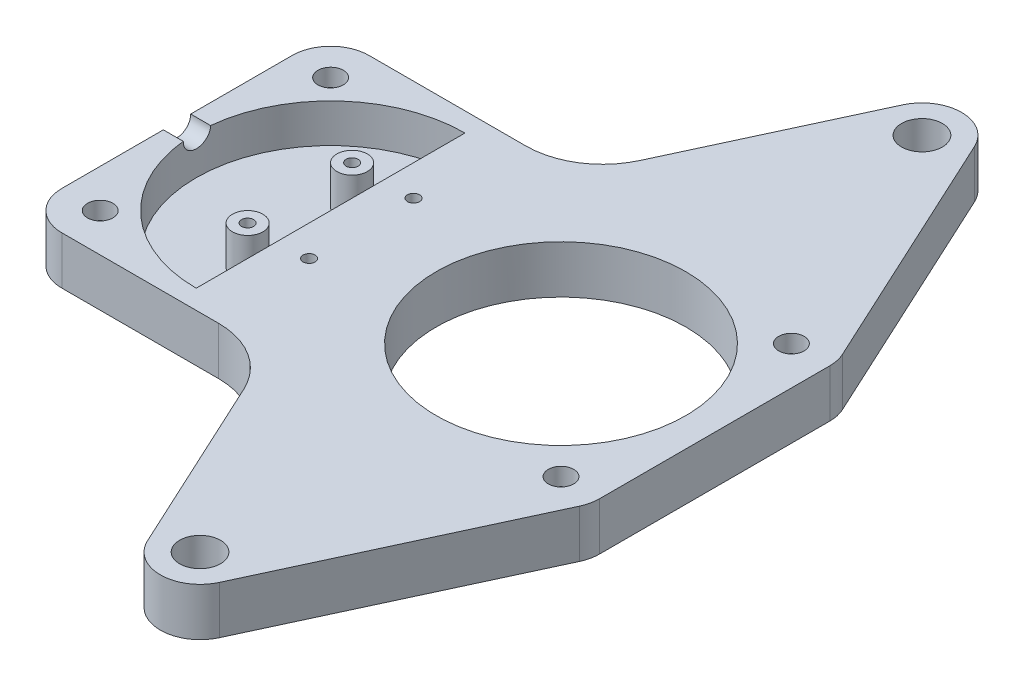
SolidWorks part; units mm, degrees
ref_plane "Front Plane" through (0, 0, 0) normal (0, 0, 1) x (1, 0, 0)
ref_plane "Top Plane" through (0, 0, 0) normal (0, 1, 0) x (1, 0, 0)
ref_plane "Right Plane" through (0, 0, 0) normal (1, 0, 0) x (0, 0, -1)
sketch "Sketch1" plane through (0, 0, 0) normal (0, 1, 0) x (1, 0, 0)
  line L0 (38.1, 19.05) -> (38.1, 25.4) construction
  line L1 (-19.05, -25.4) -> (57.15, -25.4)
  line L2 (-25.4, -19.05) -> (-25.4, 19.05)
  line L3 (-19.05, 25.4) -> (57.15, 25.4)
  line L4 (63.5, -19.05) -> (63.5, 19.05)
  line L5 (-25.4, -25.4) -> (63.5, 25.4) construction
  line L6 (-25.4, 25.4) -> (63.5, -25.4) construction
  line L7 (57.15, 0) -> (63.5, 0) construction
  line L9 (-7.62, -11.176) -> (7.62, -11.176) construction
  line L10 (-7.62, -11.176) -> (-7.62, 11.176) construction
  line L11 (-7.62, 11.176) -> (7.62, 11.176) construction
  line L12 (7.62, -11.176) -> (7.62, 11.176) construction
  line L13 (-7.62, -11.176) -> (7.62, 11.176) construction
  line L14 (-7.62, 11.176) -> (7.62, -11.176) construction
  circle A0 centre (0, 0) radius 19.05 construction
  circle A1 centre (38.1, 0) radius 19.05 construction
  circle A2 centre (38.1, 0) radius 12.7 construction
  circle A3 centre (38.1, 0) radius 20.6375
  arc A4 (-25.4, 19.05) -> (-19.05, 25.4) centre (-19.05, 19.05) cw
  arc A5 (-19.05, -25.4) -> (-25.4, -19.05) centre (-19.05, -19.05) cw
  arc A6 (57.15, -25.4) -> (63.5, -19.05) centre (57.15, -19.05) ccw
  arc A7 (57.15, 25.4) -> (63.5, 19.05) centre (57.15, 19.05) cw
  circle A8 centre (-19.05, 19.05) radius 2.1
  circle A9 centre (-19.05, -19.05) radius 2.1
  circle A10 centre (57.15, -19.05) radius 2.1
  circle A11 centre (57.15, 19.05) radius 2.1
  point P6 (19.05, 0)
  dimension "D1" = 38.1
  dimension "D2" = 38.1
  dimension "D3" = 50.8
  dimension "D7" = 25.4
  dimension "D8" = 41.275
  dimension "D9" = 6.35
  dimension "D10" = 4.2
  dimension "D4" = 88.9
  dimension "D5" = 15.24
  dimension "D6" = 22.352
extrude "Boss-Extrude1" add sketch "Sketch1" along normal blind 7.9248
sketch "Sketch2" plane through (0, 7.9248, 0) normal (0, 1, 0) x (1, 0, 0)
  line L0 (0, 22.225) -> (38.1, 22.225)
  line L1 (38.1, -22.225) -> (0, -22.225)
  arc A0 (0, 22.225) -> (0, -22.225) centre (0, 0) ccw
  arc A1 (38.1, -22.225) -> (38.1, 22.225) centre (38.1, 0) ccw
  dimension "D1" = 44.45
extrude "Cut-Extrude1" cut sketch "Sketch2" against normal offset from surface (6.4008 mm away) 1.524 up to face at (57.15, 0, 21.15)
sketch "Sketch3" plane through (0, 1.524, 0) normal (0, 1, 0) x (1, 0, 0)
  line L0 (0, 0) -> (0, 50000) construction
  line L1 (-7.62, -11.176) -> (7.62, -11.176) construction
  line L2 (-7.62, -11.176) -> (-7.62, 11.176) construction
  line L3 (-7.62, 11.176) -> (7.62, 11.176) construction
  line L4 (7.62, -11.176) -> (7.62, 11.176) construction
  line L5 (-7.62, -11.176) -> (7.62, 11.176) construction
  line L6 (-7.62, 11.176) -> (7.62, -11.176) construction
  line L7 (0, 0) -> (50000, 0) construction
  circle A0 centre (5.08, 8.636) radius 0.997
  circle A1 centre (5.08, -8.636) radius 0.997
  circle A2 centre (-5.08, 8.636) radius 0.997
  circle A3 centre (-5.08, -8.636) radius 0.997
  circle A4 centre (-5.08, 8.636) radius 2.521
  circle A5 centre (5.08, 8.636) radius 2.521
  circle A6 centre (5.08, -8.636) radius 2.521
  circle A7 centre (-5.08, -8.636) radius 2.521
  point P0 (0, 0)
  dimension "D3" = 2.54
  dimension "D4" = 2.54
  dimension "D5" = 1.9939
  dimension "D6" = 1.524
  dimension "D1" = 22.352
  dimension "D2" = 15.24
extrude "Boss-Extrude2" add sketch "Sketch3" along normal up to surface (6.4008 mm away) up to face at (19.05, 7.9248, 0)
sketch "Sketch4" plane through (0, 1.524, 0) normal (0, 1, 0) x (1, 0, 0)
  circle A0 centre (-5.08, -8.636) radius 0.9969 construction
  circle A1 centre (5.08, -8.636) radius 0.9969
  circle A2 centre (5.08, -8.636) radius 0.997
  circle A3 centre (5.08, 8.636) radius 0.9969 construction
  circle A4 centre (-5.08, 8.636) radius 0.9969 construction
  circle A5 centre (-5.08, -8.636) radius 0.997
  circle A6 centre (5.08, 8.636) radius 0.997
  circle A7 centre (-5.08, 8.636) radius 0.997
  dimension "D1" = 0
extrude "Cut-Extrude2" cut sketch "Sketch4" against normal through all
sketch "Sketch5" plane through (0, 1.524, 0) normal (0, 1, 0) x (1, 0, 0)
  line L0 (0, 22.225) -> (0, -22.225)
  line L1 (38.1, 22.225) -> (0, 22.225) construction
  line L2 (0, -22.225) -> (38.1, -22.225) construction
  line L3 (38.1, 22.225) -> (0, 22.225)
  line L4 (0, -22.225) -> (38.1, -22.225)
  circle A0 centre (38.1, 0) radius 20.6375 construction
  circle A2 centre (38.1, 0) radius 20.6375
  arc A3 (38.1, -22.225) -> (38.1, 22.225) centre (38.1, 0) ccw
  circle A4 centre (5.08, -8.636) radius 0.9969 construction
  circle A5 centre (5.08, 8.636) radius 0.9969 construction
  circle A6 centre (5.08, -8.636) radius 0.997
  circle A7 centre (5.08, 8.636) radius 0.997
  arc A8 (38.1, -22.225) -> (38.1, 22.225) centre (38.1, 0) ccw construction
extrude "Boss-Extrude3" add sketch "Sketch5" along normal up to surface (6.4008 mm away) up to face at (19.05, 7.9248, 0)
sketch "Sketch6" plane through (0, 0, 0) normal (0, -1, 0) x (1, 0, 0)
  line L0 (38.1, 0) -> (0, 0) construction
  line L1 (38.1, 0) -> (38.1, 50000) construction
  line L5 (44.0462, 62.4445) -> (62.9118, 21.7191)
  line L6 (41.3079, 65.2463) -> (34.8921, 65.2463) construction
  line L7 (34.8921, 65.2463) -> (31.6842, 59.69) construction
  line L8 (31.6842, 59.69) -> (34.8921, 54.1338) construction
  line L9 (34.8921, 54.1338) -> (41.3079, 54.1338) construction
  line L10 (41.3079, 54.1338) -> (44.5158, 59.69) construction
  line L11 (44.5158, 59.69) -> (41.3079, 65.2463) construction
  line L12 (32.1538, 62.4445) -> (14.9933, 25.4)
  line L13 (57.15, 25.4) -> (14.9933, 25.4)
  line L14 (44.5158, -59.69) -> (41.3079, -65.2463) construction
  line L15 (41.3079, -54.1338) -> (44.5158, -59.69) construction
  line L16 (34.8921, -54.1338) -> (41.3079, -54.1338) construction
  line L17 (31.6842, -59.69) -> (34.8921, -54.1338) construction
  line L18 (34.8921, -65.2463) -> (31.6842, -59.69) construction
  line L19 (41.3079, -65.2463) -> (34.8921, -65.2463) construction
  line L20 (57.15, -25.4) -> (14.9933, -25.4)
  line L21 (32.1538, -62.4445) -> (14.9933, -25.4)
  line L22 (44.0462, -62.4445) -> (62.9118, -21.7191)
  circle A0 centre (38.1, 59.69) radius 3.3782
  arc A2 (44.0462, 62.4445) -> (38.1, 66.2432) centre (38.1, 59.69) ccw
  arc A3 (32.1538, 62.4445) -> (38.1, 66.2432) centre (38.1, 59.69) cw
  circle A10 centre (38.1, 59.69) radius 6.4158 construction
  arc A11 (63.5, 19.05) -> (57.15, 25.4) centre (57.15, 19.05) ccw construction
  arc A12 (62.9118, 21.7191) -> (57.15, 25.4) centre (57.15, 19.05) ccw
  circle A13 centre (38.1, -59.69) radius 6.4158 construction
  arc A14 (62.9118, -21.7191) -> (57.15, -25.4) centre (57.15, -19.05) cw
  arc A15 (32.1538, -62.4445) -> (38.1, -66.2432) centre (38.1, -59.69) ccw
  arc A16 (44.0462, -62.4445) -> (38.1, -66.2432) centre (38.1, -59.69) cw
  circle A17 centre (38.1, -59.69) radius 3.3782
  point P21 (38.1, 25.4)
  point P41 (38.1, -25.4)
  dimension "D1" = 6.7564
  dimension "D2" = 119.38
  dimension "D3" = 3.175
  dimension "D5" = 11.1125
extrude "Boss-Extrude4" add sketch "Sketch6" against normal up to surface (7.9248 mm away) up to face at (-11.1125, 7.9248, 0)
sketch "Sketch7" plane through (-25.4, 0, 0) normal (-1, 0, 0) x (0, 0, 1)
  line L0 (-19.05, 7.9248) -> (19.05, 7.9248) construction
  circle A0 centre (0, 7.9248) radius 2.2606
  dimension "D1" = 4.5212
extrude "Cut-Extrude3" cut sketch "Sketch7" against normal up to next
sketch "Sketch8" plane through (0, 0, 0) normal (0, -1, 0) x (1, 0, 0)
  line L1 (-17.0004, 22.6) -> (-21.0996, 22.6)
  line L2 (-21.0996, 22.6) -> (-23.1492, 19.05)
  line L3 (-23.1492, 19.05) -> (-21.0996, 15.5)
  line L4 (-21.0996, 15.5) -> (-17.0004, 15.5)
  line L5 (-17.0004, 15.5) -> (-14.9508, 19.05)
  line L6 (-14.9508, 19.05) -> (-17.0004, 22.6)
  line L7 (-17.0004, -15.5) -> (-21.0996, -15.5)
  line L8 (-21.0996, -15.5) -> (-23.1492, -19.05)
  line L9 (-23.1492, -19.05) -> (-21.0996, -22.6)
  line L10 (-21.0996, -22.6) -> (-17.0004, -22.6)
  line L11 (-17.0004, -22.6) -> (-14.9508, -19.05)
  line L12 (-14.9508, -19.05) -> (-17.0004, -15.5)
  line L13 (59.1996, -15.5) -> (55.1004, -15.5)
  line L14 (55.1004, -15.5) -> (53.0508, -19.05)
  line L15 (53.0508, -19.05) -> (55.1004, -22.6)
  line L16 (55.1004, -22.6) -> (59.1996, -22.6)
  line L17 (59.1996, -22.6) -> (61.2492, -19.05)
  line L18 (61.2492, -19.05) -> (59.1996, -15.5)
  line L19 (59.1996, 22.6) -> (55.1004, 22.6)
  line L20 (55.1004, 22.6) -> (53.0508, 19.05)
  line L21 (53.0508, 19.05) -> (55.1004, 15.5)
  line L22 (55.1004, 15.5) -> (59.1996, 15.5)
  line L23 (59.1996, 15.5) -> (61.2492, 19.05)
  line L24 (61.2492, 19.05) -> (59.1996, 22.6)
  circle A0 centre (-19.05, 19.05) radius 3.55 construction
  circle A1 centre (-19.05, -19.05) radius 3.55 construction
  circle A2 centre (57.15, -19.05) radius 3.55 construction
  circle A3 centre (57.15, 19.05) radius 3.55 construction
  dimension "D1" = 7.1
extrude "Cut-Extrude4" cut sketch "Sketch8" against normal blind 5
fillet "Fillet1" radius 12.7 2 edges at (14.9933, 3.9624, -25.4) (14.9933, 3.9624, 25.4)
